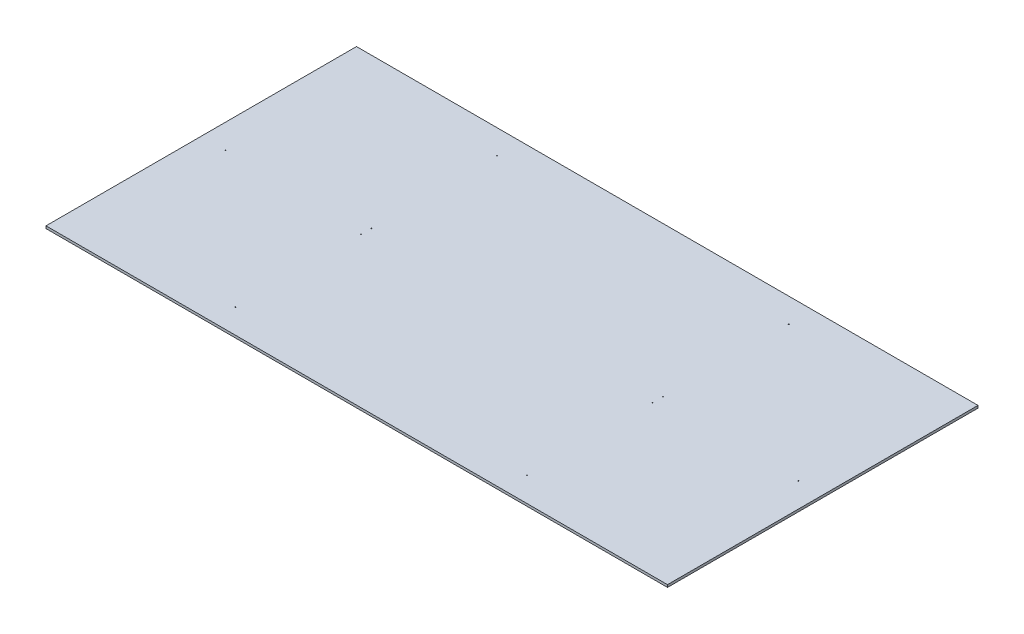
SolidWorks part; units mm, degrees
material "E-Glass Fiber"
ref_plane "Front Plane" through (0, 0, 0) normal (0, 0, 1) x (1, 0, 0)
ref_plane "Top Plane" through (0, 0, 0) normal (0, 1, 0) x (1, 0, 0)
ref_plane "Right Plane" through (0, 0, 0) normal (1, 0, 0) x (0, 0, -1)
other "Center of Mass"
sketch "Sketch1" plane through (0, 0, 0) normal (0, 1, 0) x (1, 0, 0)
  line L1 (-127.9, -63.9) -> (127.9, -63.9)
  line L2 (-127.9, -63.9) -> (-127.9, 63.9)
  line L3 (-127.9, 63.9) -> (127.9, 63.9)
  line L4 (127.9, -63.9) -> (127.9, 63.9)
  line L5 (-127.9, -63.9) -> (127.9, 63.9) construction
  line L6 (-127.9, 63.9) -> (127.9, -63.9) construction
  point P0 (0, 0)
  dimension "D1" = 127.8
  dimension "D2" = 255.8
extrude "Boss-Extrude1" add sketch "Sketch1" along normal blind 1 contours L2 L1 L4 L3
sketch "Sketch2" plane through (0, 1, 0) normal (0, 1, 0) x (1, 0, 0)
  line L0 (-127.9, -63.9) -> (-127.9, 63.9) construction
  line L1 (-127.9, -63.9) -> (127.9, -63.9) construction
  line L2 (-127.9, 0) -> (127.9, 0)
  line L4 (-127.9, 63.9) -> (127.9, 63.9) construction
  line L5 (127.9, -63.9) -> (127.9, 63.9) construction
  line L6 (0, 63.9) -> (0, -63.9)
  point P0 (-117.875, 0)
  point P10 (-60, 2.125)
  point P11 (-60, 53.875)
  point P15 (-60, -2.125)
  point P16 (-60, -53.875)
  point P17 (117.875, 0)
  point P18 (60, -53.875)
  point P19 (60, -2.125)
  point P20 (60, 2.125)
  point P21 (60, 53.875)
  dimension "D1" = 10.025
  dimension "D2" = 63.9
  dimension "D3" = 67.9
  dimension "D4" = 2.125
  dimension "D5" = 10.025
  dimension "D6" = 67.9
hole_wizard "Ø0.35 (0.35) Diameter Hole1" positions "Sketch2" profile "Sketch3" hole size "Ø0.35" standard "ANSI Metric" end condition through all
sketch "Sketch3" plane through (-117.875, 1, 0) normal (1, 0, 0) x (0, 0, 1)
  line L0 (0, 0) -> (0, 1)
  line L1 (0, 1) -> (0.175, 1)
  line L2 (0.175, 1) -> (0.175, 0)
  line L5 (0.175, 0) -> (0, 0)
  line L11 (0, -6.35) -> (0, 107.95) construction
  dimension "Thru Hole Dia." = 0.35
  dimension "Thru Hole Depth" = 1
equation "\"H\"=63.9"
